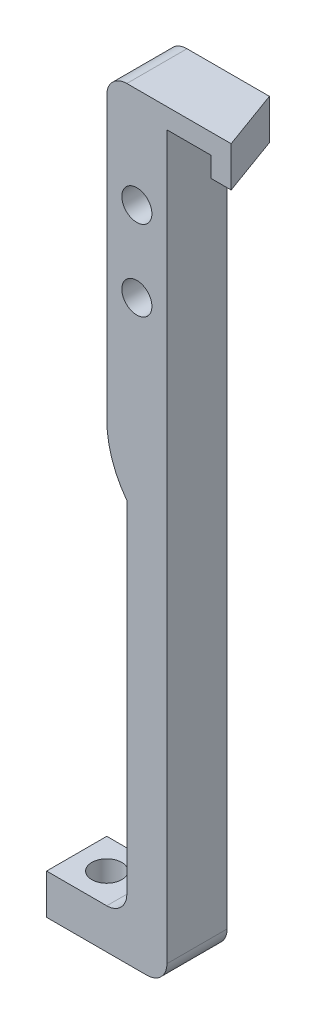
SolidWorks part; units mm, degrees
ref_plane "Front Plane" through (0, 0, 0) normal (0, 0, 1) x (1, 0, 0)
ref_plane "Top Plane" through (0, 0, 0) normal (0, 1, 0) x (1, 0, 0)
ref_plane "Right Plane" through (0, 0, 0) normal (1, 0, 0) x (0, 0, -1)
sketch "Sketch1" plane through (0, 0, 0) normal (1, 0, 0) x (0, 0, -1)
  line L1 (0, 0) -> (7.62, 0)
  line L2 (0, 0) -> (0, 96.52)
  line L3 (0, 96.52) -> (7.62, 96.52)
  line L4 (7.62, 0) -> (7.62, 96.52)
  dimension "D1" = 7.62
  dimension "D2" = 96.52
extrude "Boss-Extrude1" add sketch "Sketch1" along normal blind 7.62
sketch "Sketch2" plane through (0, 0, 0) normal (-1, 0, 0) x (0, 0, 1)
  line L0 (-7.62, 0) -> (-7.62, 96.52) construction
  line L1 (0, 0) -> (-7.62, 0)
  line L2 (0, 0) -> (0, 5.08)
  line L3 (0, 5.08) -> (-7.62, 5.08)
  line L4 (-7.62, 0) -> (-7.62, 5.08)
  dimension "D1" = 5.08
extrude "Boss-Extrude2" add sketch "Sketch2" along normal blind 7.62
sketch "Sketch4" plane through (7.62, 0, 0) normal (1, 0, 0) x (0, 0, -1)
  line L0 (7.62, 0) -> (7.62, 96.52) construction
  line L1 (0, 96.52) -> (7.62, 96.52)
  line L2 (0, 96.52) -> (0, 93.98)
  line L3 (0, 93.98) -> (7.62, 93.98)
  line L4 (7.62, 96.52) -> (7.62, 93.98)
  dimension "D1" = 2.54
extrude "Boss-Extrude3" add sketch "Sketch4" along normal blind 8.128
sketch "Sketch5" plane through (0, 93.98, 0) normal (0, -1, 0) x (1, 0, 0)
  line L1 (15.748, 0) -> (12.9745, -7.62)
  line L2 (15.748, -7.62) -> (7.62, -7.62) construction
  line L3 (15.748, 0) -> (15.748, -7.62) construction
  line L4 (10.4345, -7.62) -> (13.208, 0)
  line L5 (15.748, 0) -> (7.62, 0) construction
  line L6 (15.748, 0) -> (13.208, 0)
  line L7 (10.4345, -7.62) -> (12.9745, -7.62)
  dimension "D1" = 20
  dimension "D2" = 2.54
  dimension "D3" = 20
extrude "Boss-Extrude4" add sketch "Sketch5" along normal blind 2.54
hole_wizard "#6 Clearance Hole1" positions "Sketch7" profile "Sketch6" hole size "#6" standard "ANSI Inch" end condition up to next
sketch "Sketch7" plane through (0, 5.08, 0) normal (0, 1, 0) x (1, 0, 0)
  line L2 (0, 0) -> (0, 7.62) construction
  line L3 (-7.62, 7.62) -> (0, 7.62) construction
  point P0 (-3.81, 3.81)
  dimension "D1" = 3.81
  dimension "D2" = 3.81
sketch "Sketch6" plane through (-3.81, 5.08, -3.81) normal (1, 0, 0) x (0, 0, 1)
  line L0 (0, 0) -> (0, 5.08)
  line L1 (0, 5.08) -> (1.8986, 5.08)
  line L2 (1.8986, 5.08) -> (1.8986, 0)
  line L5 (1.8986, 0) -> (0, 0)
  line L11 (0, -6.35) -> (0, 107.95) construction
  dimension "Thru Hole Dia." = 3.7973
  dimension "Thru Hole Depth" = 5.08
sketch "Sketch8" plane through (0, 93.98, 0) normal (0, -1, 0) x (1, 0, 0)
  line L0 (15.748, -7.62) -> (12.9745, -7.62)
  line L1 (12.9745, -7.62) -> (15.748, 0)
  line L2 (15.748, 0) -> (15.748, -7.62)
extrude "Cut-Extrude1" cut sketch "Sketch8" against normal blind 2.54
ref_plane "Plane1" through (0, 0, -10.16) normal (0, 0, -1) x (-1, 0, 0)
sketch "Sketch12" plane through (0, 0, 0) normal (-1, 0, 0) x (0, 0, 1)
  line L0 (0, 96.52) -> (0, 5.08) construction
  line L1 (-7.62, 5.08) -> (0, 5.08)
  line L2 (-7.62, 5.08) -> (-7.62, 50.8)
  line L3 (-7.62, 50.8) -> (0, 50.8)
  line L4 (0, 5.08) -> (0, 50.8)
  dimension "D1" = 45.72
extrude "Cut-Extrude2" cut sketch "Sketch12" against normal blind 2.54
fillet "Fillet2" radius 12.7 1 edges at (0, 50.8, -3.81)
fillet "Fillet3" radius 2.54 3 edges at (2.54, 5.08, -3.81) (7.62, 0, -3.81) (0, 96.52, -3.81)
sketch "Sketch14" plane through (0, 0, 0) normal (0, 0, 1) x (1, 0, 0)
  line L0 (0, 93.98) -> (0, 58.42) construction
  line L1 (15.748, 96.52) -> (2.54, 96.52) construction
  circle A0 centre (3.81, 83.82) radius 1.905
  circle A1 centre (3.81, 73.66) radius 1.905
  dimension "D5" = 3.81
  dimension "D6" = 3.81
  dimension "D1" = 3.81
  dimension "D2" = 3.81
  dimension "D3" = 12.7
  dimension "D4" = 10.16
extrude "Cut-Extrude4" cut sketch "Sketch14" against normal through all
